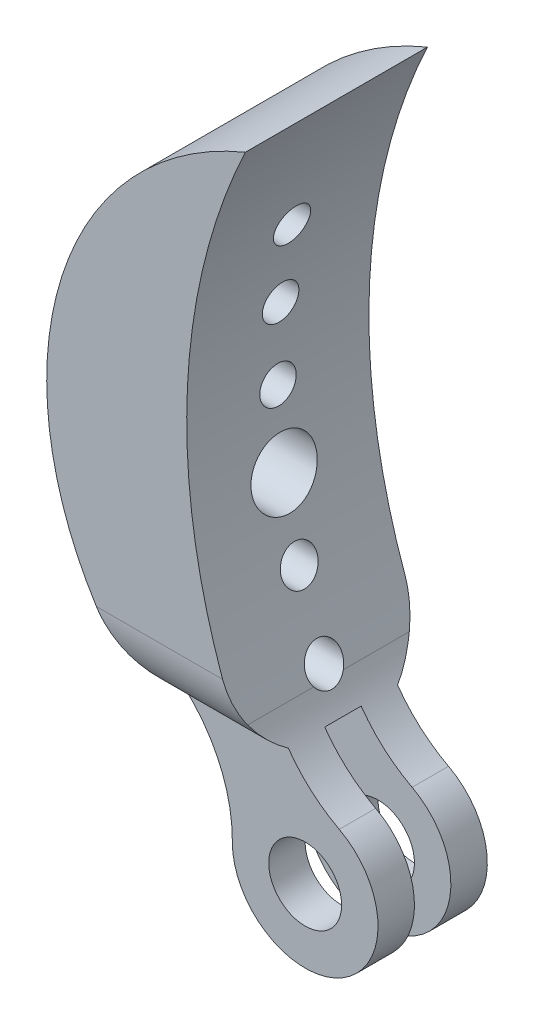
SolidWorks part; units mm, degrees
ref_plane "前视基准面" through (0, 0, 0) normal (0, 0, 1) x (1, 0, 0)
ref_plane "上视基准面" through (0, 0, 0) normal (0, 1, 0) x (1, 0, 0)
ref_plane "右视基准面" through (0, 0, 0) normal (1, 0, 0) x (0, 0, -1)
other "Configuration Table"
sketch "Sketch1" plane through (0, 0, 0) normal (0, 0, 1) x (1, 0, 0)
  line L0 (-5, 0) -> (-5, 5)
  line L1 (0, 0) -> (0, 5)
  line L2 (0, 5) -> (-5, 5)
  circle A0 centre (0, 0) radius 5
  circle A1 centre (0, 0) radius 2.5
  dimension "D1" = 5
  dimension "D2" = 10
  dimension "D3" = 5
extrude "Boss-Extrude1" add sketch "Sketch1" along normal mid plane 12.5 contours A0 L1 L2 L0 | A1 A0 region at (-3.8832, 3.8832, 0) region at (-3.4355, 3.4355, 0)
sketch "Sketch2" plane through (0, 0, 6.25) normal (0, 0, 1) x (1, 0, 0)
  line L0 (0, 5) -> (-5, 5) construction
  line L3 (0, 5) -> (6.766, 23.5893) construction
  line L4 (0, 5) -> (36.3731, 26) construction
  line L5 (0, 7.5) -> (0, 5) construction
  line L6 (-5, 5) -> (0, 5)
  arc A1 (-5, 0) -> (0, 5) centre (0, 0) ccw construction
  arc A2 (-5, 5) -> (-1.6053, 43.9344) centre (6.766, 23.5893) cw
  arc A3 (-1.6053, 43.9344) -> (0, 5) centre (36.3731, 26) ccw
  dimension "D1" = 42
  dimension "D2" = 22
  dimension "D3" = 20
  dimension "D4" = 40
extrude "Boss-Extrude2" add sketch "Sketch2" against normal up to surface (12.5 mm away) up to face at (-1.3215, 1.3215, -6.25)
fillet "Fillet2" radius 10 1 edges at (-5, 5, 0)
fillet "Fillet3" radius 10 1 edges at (0, 5, 0)
sketch "Sketch3" plane through (0, 0, 0) normal (1, 0, 0) x (0, 0, -1)
  line L2 (-6.25, -5) -> (6.25, -5) construction
  line L3 (0, -5) -> (0, 20) construction
  circle A0 centre (0, 20) radius 2.25
  circle A3 centre (0, 5) radius 1.25
  circle A4 centre (0, 10) radius 1.25
  circle A5 centre (0, 15) radius 1.25
  circle A6 centre (0, 20) radius 1.25
  circle A7 centre (0, 25) radius 1.25
  circle A8 centre (0, 30) radius 1.25
  circle A9 centre (0, 35) radius 1.25
  circle A10 centre (0, 40) radius 1.25
  dimension "D1" = 4.5
  dimension "D4" = 2.5
  dimension "D2" = 25
  dimension "D3" = 5
  dimension "D6" = 5
  dimension "D5" = 8
extrude "Cut-Extrude1" cut sketch "Sketch3" against normal through all both and the other way through all contours A6 | A0 A6 | A8 | A9 | A7 | L3 A5 | A5 L3 | A4 L3 | L3 A4 | L3 A3 | A3 L3 region at (0, 5, 0.5305) region at (0, 20.8589, 0.8589) region at (0, 21.546, 1.546) region at (0, 15, 0.5305) region at (0, 15, -0.5305) region at (0, 10, 0.5305) region at (0, 10, -0.5305) region at (0, 5, -0.5305) region at (0, 25, 0) region at (0, 30, 0) region at (0, 35, 0)
sketch "Sketch5" plane through (0, 0, 0) normal (1, 0, 0) x (0, 0, -1)
  line L0 (-3.75, 7.5) -> (-6.25, 7.5)
  line L1 (-3.75, -7.5) -> (3.75, -7.5)
  line L2 (-3.75, -7.5) -> (-3.75, 7.5)
  line L3 (-3.75, 7.5) -> (3.75, 7.5)
  line L4 (3.75, -7.5) -> (3.75, 7.5)
  line L5 (-3.75, -7.5) -> (3.75, 7.5) construction
  line L6 (-3.75, 7.5) -> (3.75, -7.5) construction
  line L7 (-6.25, 9.2732) -> (-6.25, 4.4186) construction
  line L8 (-6.25, 7.5) -> (-6.25, -5)
  line L9 (-6.25, -5) -> (6.25, -5)
  line L10 (6.25, -5) -> (6.25, 7.4624)
  line L11 (6.25, 7.4624) -> (3.75, 7.5)
  line L13 (-1.25, -7.5) -> (1.25, -7.5)
  line L14 (-1.25, -7.5) -> (-1.25, 7.5)
  line L15 (-1.25, 7.5) -> (1.25, 7.5)
  line L16 (1.25, -7.5) -> (1.25, 7.5)
  line L17 (-1.25, -7.5) -> (1.25, 7.5) construction
  line L18 (-1.25, 7.5) -> (1.25, -7.5) construction
  point P0 (0, 0)
  point P15 (0, 0)
  dimension "D1" = 7.5
  dimension "D2" = 15
  dimension "D3" = 2.5
extrude "Cut-Extrude2" cut sketch "Sketch5" along normal through all both and the other way through all contours L8 L9 L2 L0 | L10 L11 L4 L9 | L9 L16 L3 L14 region at (0, 1.25, 5) region at (0, 1.25, 0) region at (0, 1.2406, -4.9994)
fillet "Fillet4" radius 5 2 edges at (-4.6644, 7.4624, -6.25) (-4.6978, 7.5, 6.25)
sketch "Sketch6" plane through (0, 7.5, 0) normal (0, -1, 0) x (1, 0, 0)
  line L0 (-8.2385, 0) -> (-5.7385, 0) construction
  line L1 (-8.2385, 1.25) -> (-8.2385, -1.25) construction
  circle A0 centre (-5.7385, 0) radius 1.25
  dimension "D1" = 2.5
  dimension "D2" = 2.5
extrude "Cut-Extrude3" cut sketch "Sketch6" against normal blind 5
sketch "Sketch7" plane through (0, 0, 3.75) normal (0, 0, 1) x (1, 0, 0)
  line L0 (0, 0) -> (3.6858, 0) construction
  line L1 (0, 0) -> (5.3033, 5.3033) construction
  circle A0 centre (5.3033, 5.3033) radius 1.25
  circle A1 centre (5.3033, 5.3033) radius 2.5
  circle A2 centre (0, 0) radius 5
  circle A3 centre (0, 0) radius 2.5
  arc A4 (4.8296, -1.2941) -> (7.3055, 3.8062) centre (19.3185, -5.1764) cw
  arc A5 (-1.2941, 4.8296) -> (3.8062, 7.3055) centre (-5.1764, 19.3185) ccw
  arc A6 (-5, 0) -> (2.3401, 4.4186) centre (0, 0) ccw construction
  circle A7 centre (0, 0) radius 2.5 construction
  point P13 (0, 0)
  point P14 (0, 0)
  point P15 (-0.3984, -0.1681)
  point P16 (-24.3453, 30.0214)
  point P18 (0, 0)
  circle M1 centre (0, 0) radius 2.5
  arc M4 (-5, 0) -> (2.3401, 4.4186) centre (0, 0) ccw
  arc M5 (2.3401, 4.4186) -> (-1.1572, 7.5) centre (7.0203, 13.2558) cw
  dimension "D2" = 2.5
  dimension "D3" = 5
  dimension "D5" = 15
  dimension "D1" = 45
  dimension "D4" = 7.5
extrude "Boss-Extrude3" [suppressed] add sketch "Sketch7" against normal blind 2.5 contours A2 M4 M1 | A5 A1 M5 M4 | A5 A2 M5 | A2 A4 A1 | A1 A0
mirror "Mirror1" [suppressed] about plane through (0, 0, 0) normal (0, 0, 1)
